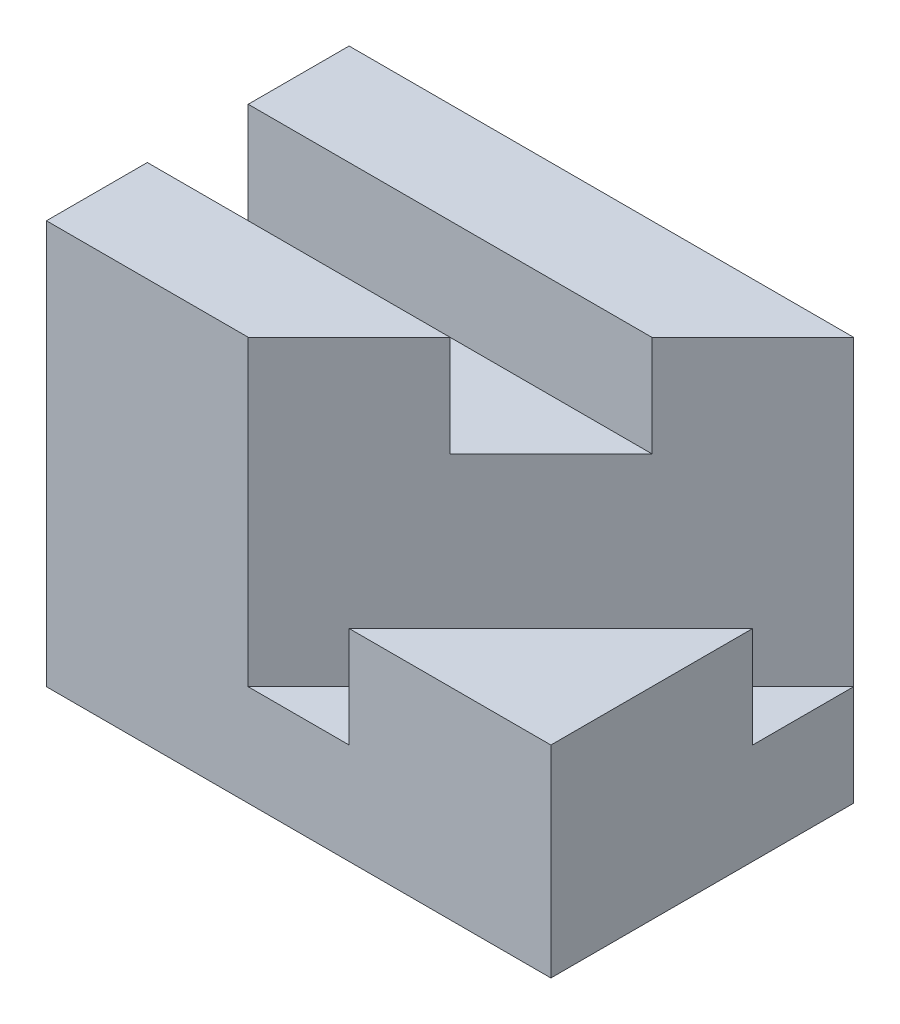
SolidWorks part; units mm, degrees
ref_plane "Front Plane" through (0, 0, 0) normal (0, 0, 1) x (1, 0, 0)
ref_plane "Top Plane" through (0, 0, 0) normal (0, 1, 0) x (1, 0, 0)
ref_plane "Right Plane" through (0, 0, 0) normal (1, 0, 0) x (0, 0, -1)
sketch "Sketch1" plane through (0, 0, 0) normal (0, 1, 0) x (1, 0, 0)
  line L1 (-25, 15) -> (25, 15)
  line L2 (-25, 15) -> (-25, -15)
  line L3 (-25, -15) -> (25, -15)
  line L4 (25, 15) -> (25, -15)
  line L5 (-25, 15) -> (25, -15) construction
  line L6 (-25, -15) -> (25, 15) construction
  point P0 (0, 0)
  dimension "D1" = 50
  dimension "D2" = 30
extrude "Boss-Extrude1" add sketch "Sketch1" along normal blind 40
sketch "Sketch2" plane through (0, 40, 0) normal (0, 1, 0) x (1, 0, 0)
  line L0 (25, -15) -> (-5, -15)
  line L1 (-25, -15) -> (25, -15) construction
  line L2 (-5, -15) -> (25, 15)
  line L3 (25, 15) -> (25, -15)
  line L4 (5, -15) -> (25, 5)
  line L5 (15, 5) -> (-25, 5)
  line L6 (-25, 15) -> (-25, -15) construction
  line L7 (5, -5) -> (-25, -5)
  line M1 (25, -15) -> (25, 15)
  line M3 (-25, 15) -> (-25, -15)
  line M4 (-25, -15) -> (25, -15)
  dimension "D1" = 20
  dimension "D2" = 20
  dimension "D3" = 10
  dimension "D4" = 10
extrude "Cut-Extrude1" cut sketch "Sketch2" against normal blind 10 contours L7 L2 L5 M3 region at (-7.381, 40, -0.2381)
extrude "Cut-Extrude2" cut sketch "Sketch2<3>" against normal blind 30 contours L4 L3 L2 M4 region at (12.3333, 40, 2.3333)
sketch "Sketch2<3>" plane through (0, 40, 0) normal (0, 1, 0) x (1, 0, 0) same geometry as "Sketch2"
extrude "Cut-Extrude3" cut sketch "Sketch2<4>" against normal blind 20 and the other way through all contours L4 L0 M1 region at (18.3333, 40, 8.3333)
sketch "Sketch2<4>" plane through (0, 40, 0) normal (0, 1, 0) x (1, 0, 0) same geometry as "Sketch2"
